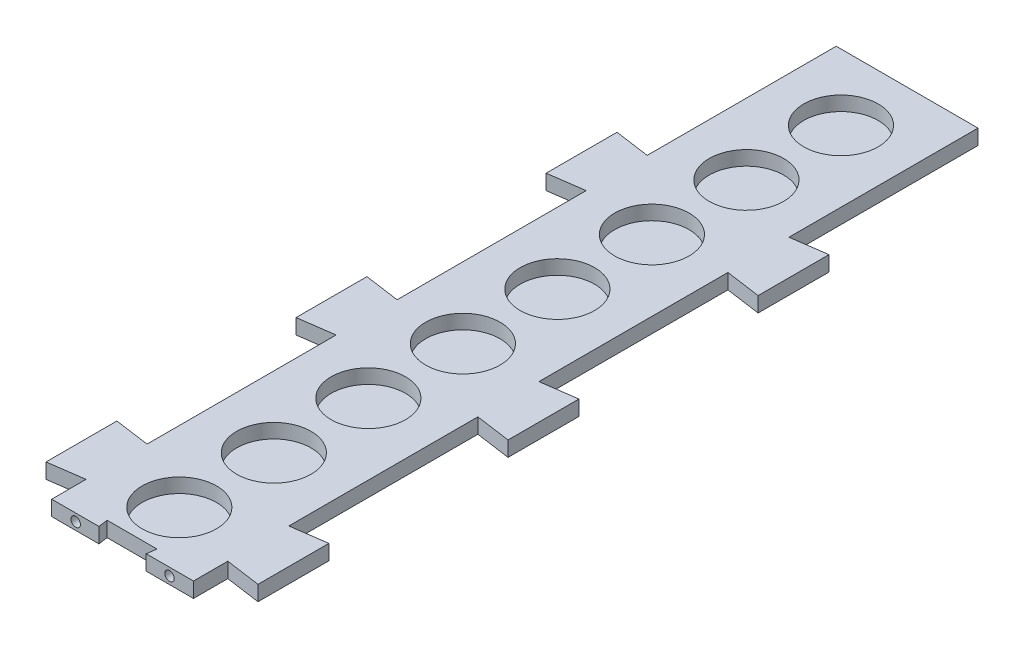
SolidWorks part; units mm, degrees
ref_plane "Front Plane" through (0, 0, 0) normal (0, 0, 1) x (1, 0, 0)
ref_plane "Top Plane" through (0, 0, 0) normal (0, 1, 0) x (1, 0, 0)
ref_plane "Right Plane" through (0, 0, 0) normal (1, 0, 0) x (0, 0, -1)
sketch "Sketch1" plane through (0, 0, 0) normal (0, 1, 0) x (1, 0, 0)
  line L1 (-19.05, -195.58) -> (19.05, -195.58)
  line L2 (-19.05, -195.58) -> (-19.05, 195.58)
  line L3 (-19.05, 195.58) -> (19.05, 195.58)
  line L4 (19.05, -195.58) -> (19.05, 195.58)
  line L5 (-19.05, -195.58) -> (19.05, 195.58) construction
  line L6 (-19.05, 195.58) -> (19.05, -195.58) construction
  point P0 (0, 0)
  dimension "D1" = 391.16
  dimension "D2" = 38.1
extrude "Boss-Extrude1" add sketch "Sketch1" along normal blind 4.064
sketch "Sketch2" plane through (0, 4.064, 0) normal (0, 1, 0) x (1, 0, 0)
  line L0 (-19.05, 195.58) -> (-19.05, -195.58) construction
  line L1 (19.05, 195.58) -> (-19.05, 195.58) construction
  line L3 (-19.05, -195.58) -> (19.05, -195.58) construction
  circle A0 centre (0, 177.8) radius 10
  circle A1 centre (0, 152.4) radius 10
  circle A2 centre (0, 127) radius 10
  circle A3 centre (0, 101.6) radius 10
  circle A4 centre (0, 76.2) radius 10
  circle A5 centre (0, 50.8) radius 10
  circle A6 centre (0, 25.4) radius 10
  circle A7 centre (0, 0) radius 10
  circle A8 centre (0, -25.4) radius 10
  circle A9 centre (0, -50.8) radius 10
  circle A10 centre (0, -76.2) radius 10
  circle A11 centre (0, -101.6) radius 10
  circle A12 centre (0, -127) radius 10
  circle A13 centre (0, -152.4) radius 10
  circle A14 centre (0, -177.8) radius 10
  dimension "D1" = 20
  dimension "D2" = 19.05
  dimension "D4" = 17.78
  dimension "D5" = 17.78
  dimension "D3" = 15
extrude "Cut-Extrude1" cut sketch "Sketch2" against normal blind 3.864
sketch "Sketch4" plane through (0, 0, 0) normal (0, 1, 0) x (1, 0, 0)
  line L0 (19.05, -56.8163) -> (28.4823, -55.4906)
  line L2 (19.05, -195.58) -> (19.05, 195.58) construction
  line L5 (19.05, 144.78) -> (19.05, 128.3812)
  line L6 (0, 195.58) -> (0, -195.58) construction
  line L7 (19.05, 195.58) -> (-19.05, 195.58) construction
  line L8 (-19.05, -195.58) -> (19.05, -195.58) construction
  line L9 (19.05, -56.8163) -> (19.05, -73.215)
  line L30 (-19.05, 144.78) -> (-19.05, 128.3812)
  line L31 (19.05, 144.78) -> (28.4823, 146.1056)
  line L32 (-19.05, 128.3812) -> (-28.4823, 127.0556)
  line L33 (19.05, 128.3812) -> (28.4823, 127.0556)
  line L34 (28.4823, 146.1056) -> (28.4823, 127.0556)
  line L35 (19.05, 144.78) -> (19.05, 128.3812)
  line L36 (19.05, 144.78) -> (19.05, 128.3812)
  line L37 (28.4823, 127.0556) -> (28.4823, 146.1056)
  line L38 (19.05, 144.78) -> (28.4823, 146.1056)
  line L39 (-19.05, 144.78) -> (-28.4823, 146.1056)
  line L40 (-28.4823, 127.0556) -> (-28.4823, 146.1056)
  line L41 (-28.4823, 146.1056) -> (-28.4823, 127.0556)
  line L42 (19.05, 77.5812) -> (28.4823, 78.9069)
  line L43 (19.05, 77.5812) -> (19.05, 61.1825)
  line L44 (19.05, 61.1825) -> (28.4823, 59.8569)
  line L45 (28.4823, 78.9069) -> (28.4823, 59.8569)
  line L46 (19.05, 10.3825) -> (28.4823, 11.7081)
  line L47 (19.05, 10.3825) -> (19.05, -6.0163)
  line L48 (19.05, -6.0163) -> (28.4823, -7.3419)
  line L49 (28.4823, 11.7081) -> (28.4823, -7.3419)
  line L50 (-19.05, 10.3825) -> (-19.05, -6.0163)
  line L51 (-19.05, -6.0163) -> (-28.4823, -7.3419)
  line L52 (-28.4823, 11.7081) -> (-28.4823, -7.3419)
  line L53 (-19.05, 10.3825) -> (-28.4823, 11.7081)
  line L54 (-19.05, 77.5812) -> (-19.05, 61.1825)
  line L55 (-19.05, 61.1825) -> (-28.4823, 59.8569)
  line L56 (-28.4823, 78.9069) -> (-28.4823, 59.8569)
  line L57 (-19.05, 77.5812) -> (-28.4823, 78.9069)
  line L58 (19.05, -73.215) -> (28.4823, -74.5406)
  line L59 (28.4823, -55.4906) -> (28.4823, -74.5406)
  line L60 (19.05, -124.015) -> (28.4823, -122.6894)
  line L61 (19.05, -124.015) -> (19.05, -140.4138)
  line L62 (19.05, -140.4138) -> (28.4823, -141.7394)
  line L63 (28.4823, -122.6894) -> (28.4823, -141.7394)
  line L72 (-19.05, -124.015) -> (-19.05, -140.4138)
  line L73 (-19.05, -140.4138) -> (-28.4823, -141.7394)
  line L74 (-28.4823, -122.6894) -> (-28.4823, -141.7394)
  line L75 (-19.05, -124.015) -> (-28.4823, -122.6894)
  line L76 (-19.05, -56.8163) -> (-19.05, -73.215)
  line L77 (-19.05, -73.215) -> (-28.4823, -74.5406)
  line L78 (-28.4823, -55.4906) -> (-28.4823, -74.5406)
  line L79 (-19.05, -56.8163) -> (-28.4823, -55.4906)
  line L80 (19.05, 144.78) -> (28.4823, 144.78) construction
  line L81 (19.05, 128.3812) -> (28.4823, 128.3812) construction
  dimension "D1" = 8
  dimension "D2" = 8
  dimension "D3" = 9.525
  dimension "D4" = 19.05
  dimension "D5" = 50.8
  dimension "D6" = 5
  dimension "D7" = 50.8
extrude "Boss-Extrude2" add sketch "Sketch4" along normal blind 4.064 contours L54 L57 L56 L55 | L50 L53 L52 L51 | L49 L46 L47 L48 | L40 L32 L30 L39 | L34 L31 L5 L33 | L45 L44 L43 L42 | L76 L77 L78 L79 | L0 L59 L58 L9 | L60 L63 L62 L61 | L72 L73 L74 L75 region at (23.8837, 0, -136.5806) region at (-23.8837, 0, -136.5806) region at (23.8837, 0, -2.1831) region at (-23.8837, 0, -2.1831) region at (-23.8837, 0, -69.3819)
sketch "Sketch5" plane through (0, 0, 195.58) normal (0, 0, 1) x (1, 0, 0)
  line L1 (-28.4823, 0) -> (28.4823, 0)
  line L2 (-28.4823, 0) -> (-28.4823, 4.064)
  line L3 (-28.4823, 4.064) -> (28.4823, 4.064)
  line L4 (28.4823, 0) -> (28.4823, 4.064)
extrude "Cut-Extrude2" cut sketch "Sketch5" against normal blind 182.88
sketch "Sketch6" plane through (0, 4.064, 0) normal (0, 1, 0) x (1, 0, 0)
  line L0 (-6.707, -12.7) -> (-6.35, -15.24)
  line L1 (19.05, -12.7) -> (-19.05, -12.7) construction
  line L2 (-6.35, -15.24) -> (-19.05, -15.24)
  line L3 (-19.05, -15.24) -> (-19.05, -12.7)
  line L4 (-6.707, -12.7) -> (-6.707, -15.24) construction
  line L5 (19.05, -12.7) -> (19.05, -15.24)
  line L6 (19.05, -15.24) -> (6.35, -15.24)
  line L7 (6.35, -15.24) -> (6.707, -12.7)
  line L8 (6.707, -12.7) -> (6.707, -15.24) construction
  line L9 (-19.05, -12.7) -> (-6.707, -12.7)
  line L10 (6.707, -12.7) -> (19.05, -12.7)
  dimension "D1" = 8
  dimension "D2" = 12.7
  dimension "D3" = 2.54
  dimension "D4" = 8
  dimension "D5" = 2.54
  dimension "D6" = 12.7
extrude "Boss-Extrude3" add sketch "Sketch6" against normal blind 4.064
sketch "Sketch7" plane through (0, 0, 15.24) normal (0, 0, 1) x (1, 0, 0)
  line L0 (-28.4823, 4.064) -> (-28.4823, 0) construction
  line L1 (28.4823, 4.064) -> (28.4823, 0) construction
  line L2 (-19.05, 0) -> (-6.35, 0) construction
  line L3 (6.35, 0) -> (19.05, 0) construction
  circle A0 centre (-12.6073, 2.032) radius 1.27
  circle A1 centre (12.6073, 2.032) radius 1.27
  dimension "D3" = 2.54
  dimension "D4" = 2.54
  dimension "D1" = 15.875
  dimension "D2" = 15.875
  dimension "D5" = 2.032
  dimension "D6" = 2.032
extrude "Cut-Extrude3" cut sketch "Sketch7" against normal blind 12.7
